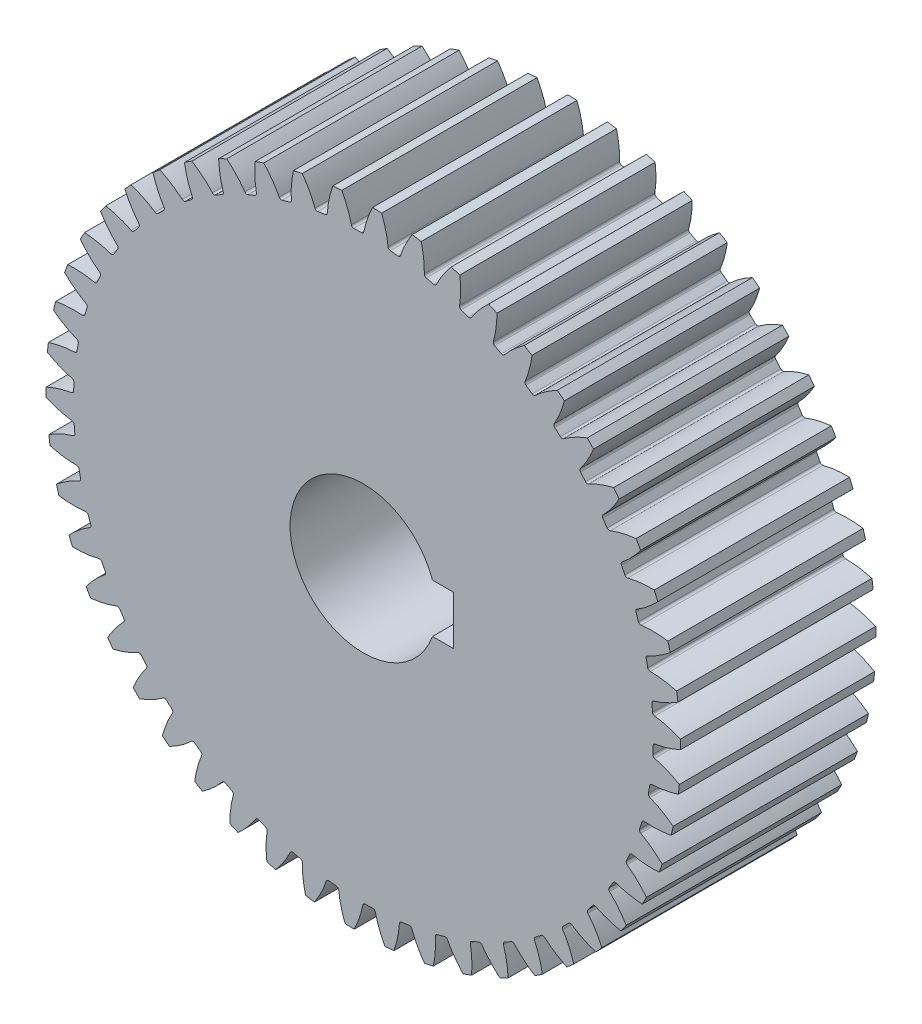
SolidWorks part; units mm, degrees
ref_plane "Front Plane" through (0, 0, 0) normal (0, 0, 1) x (1, 0, 0)
ref_plane "Top Plane" through (0, 0, 0) normal (0, 1, 0) x (1, 0, 0)
ref_plane "Right Plane" through (0, 0, 0) normal (1, 0, 0) x (0, 0, -1)
sketch "Involute Geometry" plane through (0, 0, 0) normal (0, 0, 1) x (1, 0, 0)
  line L0 (0, 23.4923) -> (0, 0) construction
  line L1 (0, 0) -> (1.125, 25.9757) construction
  line L2 (2.031, 23.4044) -> (0, 0) construction
  line L3 (0.3366, 24.9977) -> (0, 0) construction
  line L4 (0, 0) -> (1.8258, 24.9332) construction
  circle A1 centre (0, 0) radius 23.4923 construction
  circle A2 centre (0, 0) radius 25 construction
  circle A3 centre (0, 0) radius 26 construction
  circle A4 centre (0, 0) radius 23.75 construction
  arc A5 (0.7536, 25.9891) -> (1.4961, 25.9569) centre (0, 0) cw
  arc A6 (0.3366, 24.9977) -> (1.8258, 24.9332) centre (0, 0) cw construction
  spline S0 degree 4 poles (0, 23.4923) (0, 23.5114) (0.0013, 23.5648) (0.0089, 23.6656) (0.0287, 23.8296) (0.081, 24.1325) (0.1926, 24.5862) (0.3554, 25.0766) (0.5626, 25.5852) (0.7677, 26.0245) (0.9438, 26.37) (1.171, 26.7822) (1.4642, 27.2682) (1.8332, 27.8211) (2.2875, 28.4323) (2.7797, 29.0321) (3.2982, 29.6089) (3.8411, 30.1634) (4.4053, 30.6951) (4.9175, 31.1416) (5.3665, 31.5096) (5.7503, 31.8087) (6.0572, 32.04) (6.3766, 32.2711) (6.6846, 32.4876) (7.0225, 32.7147) (7.3185, 32.909) (7.7622, 33.1868) (8.0307, 33.348) (8.4647, 33.6019) (8.6612, 33.7084) (8.8384, 33.8077) (8.891, 33.8352) (8.9294, 33.8561) (8.9501, 33.8675) knots 0 0 0 0 0 0.005377 0.015084 0.028532 0.04661 0.092111 0.146842 0.174209 0.201575 0.228941 0.256307 0.307035 0.361767 0.4165 0.471232 0.525964 0.580697 0.635429 0.690161 0.717528 0.744894 0.77226 0.799626 0.826992 0.854358 0.881725 0.909091 0.954545 0.977273 0.988636 0.994318 1 1 1 1 1 construction
  spline S1 degree 4 poles (0, 23.4923) (0, 23.5114) (0.0013, 23.5648) (0.0089, 23.6656) (0.0287, 23.8296) (0.081, 24.1325) (0.1926, 24.5862) (0.3554, 25.0766) (0.5626, 25.5852) (0.7677, 26.0245) (0.9438, 26.37) (1.171, 26.7822) (1.4642, 27.2682) (1.8332, 27.8211) (2.2875, 28.4323) (2.7797, 29.0321) (3.2982, 29.6089) (3.8411, 30.1634) (4.4053, 30.6951) (4.9175, 31.1416) (5.3665, 31.5096) (5.7503, 31.8087) (6.0572, 32.04) (6.3766, 32.2711) (6.6846, 32.4876) (7.0225, 32.7147) (7.3185, 32.909) (7.6041, 33.0878) (7.7558, 33.1811) (7.8311, 33.2268) knots 0 0 0 0 0 0.005377 0.015084 0.028532 0.04661 0.092111 0.146842 0.174209 0.201575 0.228941 0.256307 0.307035 0.361767 0.4165 0.471232 0.525964 0.580697 0.635429 0.690161 0.717528 0.744894 0.77226 0.799626 0.826992 0.854358 0.881725 0.909091 0.909091 0.909091 0.909091 0.909091
  spline S3 degree 4 poles (2.031, 23.4044) (2.0327, 23.4233) (2.036, 23.4767) (2.0371, 23.5778) (2.0316, 23.7428) (2.0056, 24.0491) (1.9337, 24.5108) (1.8139, 25.0134) (1.6514, 25.5381) (1.4851, 25.9934) (1.3395, 26.3529) (1.1488, 26.7831) (0.8988, 27.2927) (0.5789, 27.8754) (0.1792, 28.5237) (-0.2593, 29.1637) (-0.726, 29.7832) (-1.219, 30.3825) (-1.7351, 30.961) (-2.2068, 31.4501) (-2.6223, 31.8556) (-2.9787, 32.1868) (-3.2645, 32.4437) (-3.5628, 32.7016) (-3.8509, 32.9439) (-4.1678, 33.1993) (-4.446, 33.4185) (-4.864, 33.7336) (-5.1175, 33.9174) (-5.528, 34.2079) (-5.7146, 34.331) (-5.8825, 34.4453) (-5.9325, 34.4771) (-5.969, 34.5013) (-5.9886, 34.5144) knots 0 0 0 0 0 0.005377 0.015084 0.028532 0.04661 0.092111 0.146842 0.174209 0.201575 0.228941 0.256307 0.307035 0.361767 0.4165 0.471232 0.525964 0.580697 0.635429 0.690161 0.717528 0.744894 0.77226 0.799626 0.826992 0.854358 0.881725 0.909091 0.954545 0.977273 0.988636 0.994318 1 1 1 1 1 construction
  spline S4 degree 4 poles (2.031, 23.4044) (2.0327, 23.4233) (2.036, 23.4767) (2.0371, 23.5778) (2.0316, 23.7428) (2.0056, 24.0491) (1.9337, 24.5108) (1.8139, 25.0134) (1.6514, 25.5381) (1.4851, 25.9934) (1.3395, 26.3529) (1.1488, 26.7831) (0.8988, 27.2927) (0.5789, 27.8754) (0.1792, 28.5237) (-0.2593, 29.1637) (-0.726, 29.7832) (-1.219, 30.3825) (-1.7351, 30.961) (-2.2068, 31.4501) (-2.6223, 31.8556) (-2.9787, 32.1868) (-3.2645, 32.4437) (-3.5628, 32.7016) (-3.8509, 32.9439) (-4.1678, 33.1993) (-4.446, 33.4185) (-4.7151, 33.6213) (-4.8581, 33.7274) (-4.9292, 33.7794) knots 0 0 0 0 0 0.005377 0.015084 0.028532 0.04661 0.092111 0.146842 0.174209 0.201575 0.228941 0.256307 0.307035 0.361767 0.4165 0.471232 0.525964 0.580697 0.635429 0.690161 0.717528 0.744894 0.77226 0.799626 0.826992 0.854358 0.881725 0.909091 0.909091 0.909091 0.909091 0.909091
  dimension "D5" = 3.417
sketch "Sketch2" plane through (0, 0, 0) normal (0, 0, 1) x (1, 0, 0)
  circle A0 centre (0, 0) radius 23.75 construction
  circle A1 centre (0, 0) radius 23.75
extrude "Boss-Extrude1" add sketch "Sketch2" along normal mid plane 16
sketch "Sketch3" plane through (0, 0, 0) normal (0, 0, 1) x (1, 0, 0)
  arc A3 (0.0199, 23.75) -> (2.0335, 23.6628) centre (0, 0) cw
  arc A4 (1.4961, 25.9569) -> (0.7536, 25.9891) centre (0, 0) ccw construction
  arc A5 (1.4961, 25.9569) -> (0.7536, 25.9891) centre (0, 0) ccw
  circle A7 centre (0, 0) radius 23.75 construction
  spline S0 degree 4 poles (999.8204, 40.2462) (20.7121, 20.125) (0.4503, 21.1025) (-0.1347, 22.474) (0.0287, 23.8296) (0.081, 24.1325) (0.1926, 24.5862) (0.3554, 25.0766) (0.5626, 25.5852) (0.7677, 26.0245) (0.9438, 26.37) (1.171, 26.7822) (1.4642, 27.2682) (1.8332, 27.8211) (2.2875, 28.4323) (2.7797, 29.0321) (3.2982, 29.6089) (3.8411, 30.1634) (4.4053, 30.6951) (4.9175, 31.1416) (5.3665, 31.5096) (5.7503, 31.8087) (6.0572, 32.04) (6.3766, 32.2711) (6.6846, 32.4876) (7.0225, 32.7147) (8.3806, 33.6059) (11.7895, 35.5553) (-19.6779, 16.1915) (862.8738, 551.731) knots -0.338747 -0.338747 -0.338747 -0.338747 -0.338747 0.005377 0.015084 0.028532 0.04661 0.092111 0.146842 0.174209 0.201575 0.228941 0.256307 0.307035 0.361767 0.4165 0.471232 0.525964 0.580697 0.635429 0.690161 0.717528 0.744894 0.77226 0.799626 0.826992 0.854358 0.881725 1.301773 1.301773 1.301773 1.301773 1.301773 only from (0, 23.4923) to (7.5082, 22.3415) construction
  spline S1 degree 4 poles (0.0199, 23.75) (0.0244, 23.7861) (0.0384, 23.8856) (0.0837, 24.1434) (0.1926, 24.5862) (0.3677, 25.1136) (0.5556, 25.5675) (0.6944, 25.8667) (0.7536, 25.9891) knots 0.018251 0.018251 0.018251 0.018251 0.018251 0.028532 0.04661 0.092111 0.146842 0.185208 0.185208 0.185208 0.185208 0.185208
  spline S3 degree 4 poles (-992.5974, 126.5343) (-18.8947, 21.8403) (1.3758, 21.0624) (2.0772, 22.3782) (2.0316, 23.7428) (2.0056, 24.0491) (1.9337, 24.5108) (1.8139, 25.0134) (1.6514, 25.5381) (1.4851, 25.9934) (1.3395, 26.3529) (1.1488, 26.7831) (0.8988, 27.2927) (0.5789, 27.8754) (0.1792, 28.5237) (-0.2593, 29.1637) (-0.726, 29.7832) (-1.219, 30.3825) (-1.7351, 30.961) (-2.2068, 31.4501) (-2.6223, 31.8556) (-2.9787, 32.1868) (-3.2645, 32.4437) (-3.5628, 32.7016) (-3.8509, 32.9439) (-4.1678, 33.1993) (-5.4438, 34.2046) (-8.6715, 36.4414) (21.0041, 14.4296) (-811.9435, 624.2644) knots -0.338747 -0.338747 -0.338747 -0.338747 -0.338747 0.005377 0.015084 0.028532 0.04661 0.092111 0.146842 0.174209 0.201575 0.228941 0.256307 0.307035 0.361767 0.4165 0.471232 0.525964 0.580697 0.635429 0.690161 0.717528 0.744894 0.77226 0.799626 0.826992 0.854358 0.881725 1.301773 1.301773 1.301773 1.301773 1.301773 only from (2.031, 23.4044) to (-4.9292, 33.7794) construction
  spline S4 degree 4 poles (2.0335, 23.6628) (2.0321, 23.6992) (2.0267, 23.7995) (2.0039, 24.0602) (1.9337, 24.5108) (1.8049, 25.0514) (1.6569, 25.5198) (1.5445, 25.8299) (1.4961, 25.9569) knots 0.018251 0.018251 0.018251 0.018251 0.018251 0.028532 0.04661 0.092111 0.146842 0.185208 0.185208 0.185208 0.185208 0.185208
extrude "Boss-Extrude2" add sketch "Sketch3" along normal through all and the other way through all
fillet "Fillet2" radius 0.2 2 edges at (0.0199, 23.75, 0) (2.0335, 23.6628, 0)
pattern_circular "CirPattern1" count 50 over 360 about axis through (0, 0, 8) along (0, 0, -1) of "Boss-Extrude2", "Fillet2"
ref_axis "Axis1" through (0, 0, 8) along (0, 0, -1)
sketch "Sketch4" plane through (0, 0, -8) normal (0, 0, -1) x (-1, 0, 0)
  circle A1 centre (0, 0) radius 6.0045
  dimension "D1" = 12.009
extrude "Cut-Extrude1" cut sketch "Sketch4" against normal through all
sketch "Sketch5" plane through (0, 0, -8) normal (0, 0, -1) x (-1, 0, 0)
  line L7 (-7.4045, -2) -> (-3.4045, -2)
  line L8 (-7.4045, -2) -> (-7.4045, 2)
  line L9 (-7.4045, 2) -> (-3.4045, 2)
  line L10 (-3.4045, -2) -> (-3.4045, 2)
  line L11 (-7.4045, -2) -> (-3.4045, 2) construction
  line L12 (-7.4045, 2) -> (-3.4045, -2) construction
  circle A3 centre (0, 0) radius 6.0045 construction
  point P7 (-5.4045, 0)
  dimension "D1" = 2.6
  dimension "D3" = 4
extrude "Cut-Extrude2" cut sketch "Sketch5" against normal through all
equation "\"N\"= 50'Number of Teeth"
equation "\"m\"= 1mm'Diametral Pitch"
equation "\"phi\"= 20deg'Pressure Angle"
equation "\"a\"= \"m\"'Addendum"
equation "\"b\"= 1.25 * \"m\"'Dedendum"
equation "\"Dp\"= \"N\" * \"m\"'Pitch diameter"
equation "\"Db\"= \"Dp\" * cos ( \"phi\" )'Base diameter"
equation "\"D1@Involute Geometry\" = \"Db\""
equation "\"D2@Involute Geometry\" = \"Dp\""
equation "\"D3@Involute Geometry\" = \"Dp\" + 2 * \"a\""
equation "\"D4@Involute Geometry\" = \"Dp\" - 2 * \"b\""
equation "\"D1@CirPattern1\"=\"N\""
equation "\"D5@Involute Geometry\"=180/\"N\"-\"j_th\"/2"
equation "\"D1@Boss-Extrude1\"=16*\"m\""
equation "\"j_th\"= ( 360deg ) * ( 0.16mm ) / ( pi * \"Dp\" )'Angular backlash"
equation "\"alpha\"= sqr ( \"Dp\" ^ 2 - \"Db\" ^ 2 ) / \"Db\" * 180 / pi - \"phi\""
equation "\"beta\"= ( ( 360deg / \"N\" ) / 4 - \"alpha\" )"
